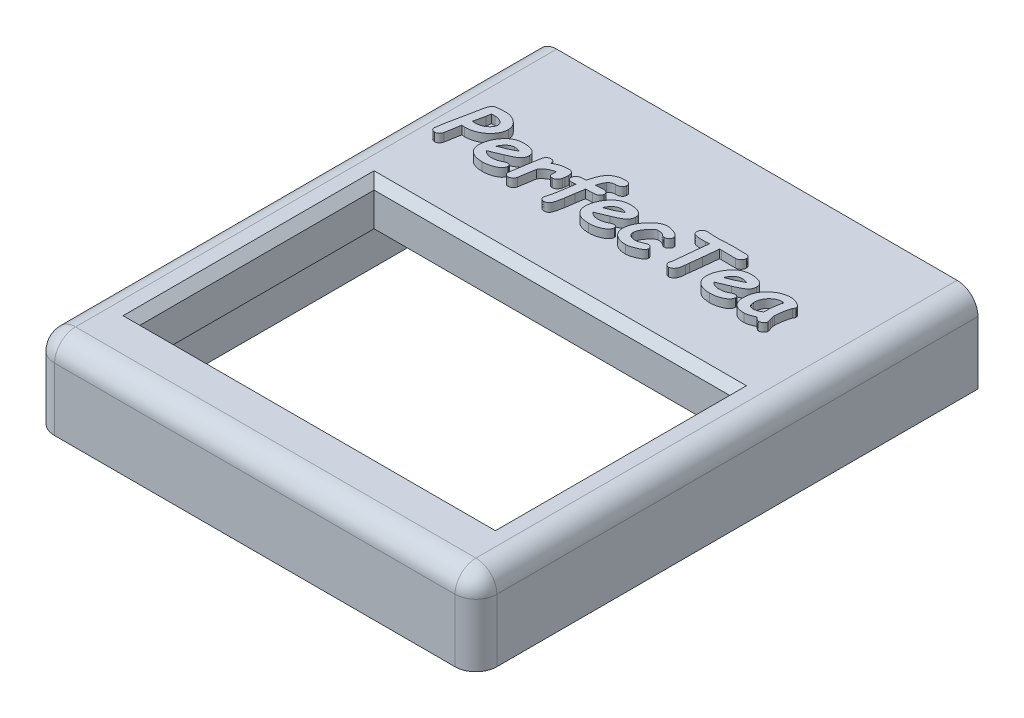
SolidWorks part; units mm, degrees
ref_plane "Front Plane" through (0, 0, 0) normal (0, 0, 1) x (1, 0, 0)
ref_plane "Top Plane" through (0, 0, 0) normal (0, 1, 0) x (1, 0, 0)
ref_plane "Right Plane" through (0, 0, 0) normal (1, 0, 0) x (0, 0, -1)
sketch "Sketch1" plane through (0, 0, 0) normal (0, 1, 0) x (1, 0, 0)
  line L0 (0, 60) -> (0, -60) construction
  line L1 (-52.85, 60) -> (52.85, 60)
  line L2 (-52.85, 60) -> (-52.85, -60)
  line L3 (-52.85, -60) -> (52.85, -60)
  line L4 (52.85, 60) -> (52.85, -60)
  line L5 (-52.85, 0) -> (52.85, 0) construction
  point P8 (0, 0)
  dimension "D1" = 120
  dimension "D2" = 105.7
extrude "Boss-Extrude1" add sketch "Sketch1" against normal blind 25
sketch "Sketch2" plane through (0, 0, 0) normal (0, 1, 0) x (1, 0, 0)
  line L0 (-52.85, -45) -> (52.85, -45) construction
  line L1 (-52.85, 60) -> (-52.85, -60) construction
  line L2 (52.85, -60) -> (52.85, 60) construction
  line L3 (-52.85, -60) -> (52.85, -60) construction
  line L4 (-52.85, 11) -> (52.85, 11) construction
  line L5 (-42.4862, 11) -> (-42.4862, -45) construction
  line L6 (42.5138, -45) -> (42.5138, 11) construction
  line L7 (-47.85, 60) -> (-47.85, -60) construction
  line L8 (52.85, 60) -> (-52.85, 60) construction
  line L9 (47.85, 60) -> (47.85, -60) construction
  line L10 (-45.85, 60) -> (-45.85, -60) construction
  line L11 (45.85, 60) -> (45.85, -60) construction
  line L13 (-42.4862, 11) -> (42.5138, 11)
  line L14 (-42.4862, 11) -> (-42.4862, -45)
  line L15 (-42.4862, -45) -> (42.5138, -45)
  line L16 (42.5138, 11) -> (42.5138, -45)
  point P23 (42.5138, -45)
  dimension "D1" = 15
  dimension "D2" = 56
  dimension "D4" = 10.3638
  dimension "D5" = 5
  dimension "D6" = 5
  dimension "D7" = 2
  dimension "D8" = 2
  dimension "D9" = 85
extrude "Cut-Extrude1" cut sketch "Sketch2" against normal blind 25
sketch "Sketch3" plane through (0, -25, 0) normal (0, -1, 0) x (1, 0, 0)
  line L0 (-42.4862, -11) -> (-42.4862, -60) construction
  line L1 (52.85, -60) -> (-52.85, -60) construction
  line L2 (42.5138, -11) -> (42.5138, -60) construction
  line L3 (-42.4862, -13) -> (42.5138, -13) construction
  line L4 (42.5138, -11) -> (-42.4862, -11) construction
  line L5 (-47.55, -60) -> (-47.55, 60) construction
  line L6 (-52.85, 60) -> (52.85, 60) construction
  line L7 (47.55, 60) -> (47.55, -60) construction
  line L8 (52.85, 60) -> (52.85, -60) construction
  line L9 (-52.85, -60) -> (-52.85, 60) construction
  line L10 (-52.85, -54.7) -> (52.85, -54.7) construction
  line L11 (-52.85, 54.7) -> (52.85, 54.7) construction
  line L13 (-52.85, 60) -> (-47.55, 60)
  line L14 (-52.85, 60) -> (-52.85, -60)
  line L15 (-52.85, -60) -> (-47.55, -60)
  line L16 (-47.55, 60) -> (-47.55, -60)
  line L17 (47.55, 60) -> (52.85, 60)
  line L18 (47.55, 60) -> (47.55, -60)
  line L19 (47.55, -60) -> (52.85, -60)
  line L20 (52.85, 60) -> (52.85, -60)
  line L21 (-47.55, 60) -> (47.55, 60)
  line L22 (-47.55, 60) -> (-47.55, 54.7)
  line L23 (-47.55, 54.7) -> (47.55, 54.7)
  line L24 (47.55, 60) -> (47.55, 54.7)
  line L25 (-47.55, -54.7) -> (47.55, -54.7)
  line L26 (-47.55, -54.7) -> (-47.55, -60)
  line L27 (-47.55, -60) -> (47.55, -60)
  line L28 (47.55, -54.7) -> (47.55, -60)
  point P26 (47.55, 54.7)
  point P28 (47.55, -54.7)
  point P29 (-47.55, -54.7)
  point P30 (-47.55, 54.7)
  line M9 (-52.85, 60) -> (-52.85, -60)
  line M10 (-52.85, -60) -> (52.85, -60)
  line M11 (52.85, -60) -> (52.85, 60)
  line M12 (52.85, 60) -> (-52.85, 60)
  dimension "D1" = 2
  dimension "D2" = 5.3
  dimension "D3" = 5.3
  dimension "D4" = 5.3
  dimension "D5" = 5.3
extrude "Cut-Extrude3" cut sketch "Sketch3" against normal blind 5 contours L16 M12 M9 M10 | L16 L23 L18 M12 | L18 M12 M10 M11 | L25 L16 L18 M10 region at (-50.2, -25, 0) region at (0, -25, 57.35) region at (50.2, -25, 0) region at (0, -25, -57.35)
sketch "Sketch5" plane through (0, -25, 0) normal (0, -1, 0) x (1, 0, 0)
  line L0 (-42.4862, -11) -> (-42.4862, -54.7) construction
  line L1 (-47.55, -54.7) -> (47.55, -54.7) construction
  line L2 (42.5138, -11) -> (42.5138, -54.7) construction
  line L3 (-42.4862, -13) -> (42.5138, -13) construction
  line L4 (42.5138, -11) -> (-42.4862, -11) construction
  line L5 (42.5138, -49.7) -> (-42.4862, -49.7) construction
  line L6 (-47.55, -54.7) -> (47.55, -54.7) construction
  line L8 (42.5138, -49.7) -> (-42.4862, -49.7)
  line L9 (42.5138, -49.7) -> (42.5138, -13)
  line L10 (42.5138, -13) -> (-42.4862, -13)
  line L11 (-42.4862, -49.7) -> (-42.4862, -13)
  dimension "D1" = 2
  dimension "D2" = 5
extrude "Cut-Extrude4" cut sketch "Sketch5" against normal blind 23 contours L10 L11 L8 L9
fillet "Fillet2" radius 5 1 edges at (-52.85, 0, 0)
fillet "Fillet3" radius 5 4 edges at (2.5, 0, 60) (-51.3855, -1.4645, 60) (-52.85, -12.5, 60) (52.85, -10, 60)
fillet "Fillet4" radius 5 2 edges at (51.3855, -1.4645, 58.5355) (52.85, 0, -2.5)
sketch "Sketch7" plane through (0, 0, 0) normal (0, 1, 0) x (1, 0, 0)
  line L0 (0.0138, 11) -> (0, 60) construction
  line L1 (42.5138, 11) -> (-42.4862, 11) construction
  line L2 (47.85, 60) -> (-47.85, 60) construction
  text T0 "PerfecTea" font "Comic Sans MS" height in points 48
extrude "Boss-Extrude2" add sketch "Sketch7" along normal blind 2
sketch "Sketch9" plane through (0, -25, 0) normal (0, -1, 0) x (1, 0, 0)
  line L0 (-47.55, -54.7) -> (47.55, -54.7) construction
  line L1 (-47.55, 54.7) -> (47.55, 54.7) construction
  line L2 (-47.55, 54.7) -> (-47.55, -54.7) construction
  line L3 (-42.4862, -11) -> (-42.4862, -13) construction
  line L4 (42.5138, -13) -> (-42.4862, -13) construction
  line L6 (47.55, 54.7) -> (47.55, -54.7) construction
  line L7 (-45.55, -54.7) -> (-42.4862, -54.7)
  line L8 (-45.55, -54.7) -> (-45.55, 54.7)
  line L9 (-45.55, 54.7) -> (-42.4862, 54.7)
  line L10 (-42.4862, -54.7) -> (-42.4862, 54.7)
  line L11 (47.55, 54.7) -> (47.55, -54.7) construction
  line L12 (42.5138, 45) -> (42.5138, -11) construction
  line L13 (46.55, -54.7) -> (42.5138, -54.7)
  line L14 (46.55, -54.7) -> (46.55, 54.7)
  line L15 (46.55, 54.7) -> (42.5138, 54.7)
  line L16 (42.5138, -54.7) -> (42.5138, 54.7)
  line L17 (-42.4862, -11) -> (-42.4862, 45) construction
  point P0 (-45.55, -54.7)
  point P1 (-45.55, 54.7)
  point P12 (46.55, 54.7)
  point P20 (46.55, -54.7)
  dimension "D1" = 2
  dimension "D2" = 2
  dimension "D3" = 1
  dimension "D4" = 1
extrude "Cut-Extrude5" cut sketch "Sketch9" against normal up to vertex (23 mm away) up to point (42.5138, -2, -13)
sketch "Sketch12" plane through (0, -25, 0) normal (0, -1, 0) x (1, 0, 0)
  line L1 (-42.4862, -49.7) -> (42.5138, -49.7)
  line L2 (-42.4862, -49.7) -> (-42.4862, -54.7)
  line L3 (-42.4862, -54.7) -> (42.5138, -54.7)
  line L4 (42.5138, -49.7) -> (42.5138, -54.7)
extrude "Cut-Extrude6" cut sketch "Sketch12" against normal up to vertex (23 mm away) up to point (-42.4862, -2, -49.7)
sketch "Sketch13" plane through (0, -25, 0) normal (0, -1, 0) x (1, 0, 0)
  line L1 (-42.4862, 54.7) -> (42.5138, 54.7)
  line L2 (-42.4862, 54.7) -> (-42.4862, 45)
  line L3 (-42.4862, 45) -> (42.5138, 45)
  line L4 (42.5138, 54.7) -> (42.5138, 45)
extrude "Cut-Extrude7" cut sketch "Sketch13" against normal up to vertex (23 mm away) up to point (42.5138, -2, -11)
sketch "Sketch17" plane through (0, -25, 0) normal (0, -1, 0) x (1, 0, 0)
  line L0 (-42.4862, -13) -> (-42.4862, -11) construction
  line L1 (42.5138, -11) -> (-42.4862, -11) construction
  line L3 (-42.4862, -12) -> (42.5138, -12)
  line L4 (-42.4862, -12) -> (-42.4862, -13)
  line L5 (-42.4862, -13) -> (42.5138, -13)
  line L6 (42.5138, -12) -> (42.5138, -13)
  point P0 (-42.4862, -12)
  dimension "D1" = 1
extrude "Cut-Extrude8" cut sketch "Sketch17" against normal up to vertex (23 mm away) up to point (-42.4862, -2, -13)
sketch "Sketch20" plane through (0, -2, 0) normal (0, -1, 0) x (1, 0, 0)
  line L5 (-43.4862, -12) -> (-42.4862, -12)
  line L6 (43.5138, -12) -> (42.5138, -12)
  line L10 (-43.4862, 46) -> (43.5138, 46)
  line L11 (43.5138, 46) -> (43.5138, -11)
  line L12 (43.5138, -11) -> (43.5138, -12)
  line L13 (-43.4862, -12) -> (-43.4862, -11)
  line L14 (-43.4862, -11) -> (-43.4862, 46)
  line L15 (-43.4862, 46) -> (43.5138, 46)
  line L16 (43.5138, 46) -> (43.5138, -11)
  line L17 (43.5138, -11) -> (43.5138, -12)
  line L18 (-43.4862, -12) -> (-43.4862, -11)
  line L19 (-43.4862, -11) -> (-43.4862, 46)
  line L24 (42.5138, -12) -> (42.5138, -11)
  line L25 (-42.4862, -12) -> (42.5138, -12)
  line L26 (-42.4862, -11) -> (-42.4862, -12)
  line L27 (-42.4862, 45) -> (-42.4862, -11)
  line L28 (42.5138, 45) -> (-42.4862, 45)
  line L29 (42.5138, -11) -> (42.5138, 45)
  line L30 (42.5138, -12) -> (42.5138, -11)
  line L32 (-42.4862, -11) -> (-42.4862, -12)
  line L33 (-42.4862, 45) -> (-42.4862, -11)
  line L34 (42.5138, 45) -> (-42.4862, 45)
  line L35 (42.5138, -11) -> (42.5138, 45)
  point P0 (0, 0)
  dimension "D1" = 1
  dimension "D3" = 0
extrude "Boss-Extrude3" add sketch "Sketch20" along normal up to vertex (23 mm away) up to point (-42.4862, -25, -11)
sketch "Sketch21" plane through (0, 0, 54.7) normal (0, 0, -1) x (-1, 0, 0)
  line L1 (-46.55, -2) -> (45.55, -2)
  line L2 (-46.55, -2) -> (-46.55, -20)
  line L3 (-46.55, -20) -> (45.55, -20)
  line L4 (45.55, -2) -> (45.55, -20)
extrude "Cut-Extrude9" cut sketch "Sketch21" against normal blind 2
sketch "Sketch22" plane through (0, 0, -54.7) normal (0, 0, 1) x (1, 0, 0)
  line L1 (-45.55, -2) -> (46.55, -2)
  line L2 (-45.55, -2) -> (-45.55, -20)
  line L3 (-45.55, -20) -> (46.55, -20)
  line L4 (46.55, -2) -> (46.55, -20)
extrude "Cut-Extrude10" cut sketch "Sketch22" against normal blind 2
sketch "Sketch23" plane through (0, 0, 54.7) normal (0, 0, 1) x (1, 0, 0)
  line L1 (-47.55, -20) -> (-45.55, -20)
  line L2 (-47.55, -20) -> (-47.55, -25)
  line L3 (-47.55, -25) -> (-45.55, -25)
  line L4 (-45.55, -20) -> (-45.55, -25)
  line L5 (46.55, -20) -> (47.55, -20)
  line L6 (46.55, -20) -> (46.55, -25)
  line L7 (46.55, -25) -> (47.55, -25)
  line L8 (47.55, -20) -> (47.55, -25)
extrude "Boss-Extrude4" add sketch "Sketch23" along normal up to vertex (2 mm away) up to point (-45.55, -20, 56.7)
chamfer "Chamfer1" distance 2 angle 45 4 edges at (42.5138, 0, 17) (0.0138, 0, 45) (-42.4862, 0, 17) (0.0138, 0, -11)
sketch "Sketch24" plane through (-47.55, 0, 0) normal (-1, 0, 0) x (0, 0, 1)
  line L0 (-54.7, -20) -> (-54.7, -25) construction
  line L1 (56.7, -20) -> (-54.7, -20) construction
  line L3 (-54.7, -21) -> (56.7, -21)
  line L4 (-54.7, -21) -> (-54.7, -25)
  line L5 (-54.7, -25) -> (56.7, -25)
  line L6 (56.7, -21) -> (56.7, -25)
  point P0 (-54.7, -21)
  dimension "D1" = 1
extrude "Cut-Extrude11" cut sketch "Sketch24" against normal up to vertex (2 mm away) up to point (-45.55, -25, -54.7)
sketch "Sketch25" plane through (47.55, 0, 0) normal (1, 0, 0) x (0, 0, -1)
  line L0 (-56.7, -25) -> (-56.7, -20) construction
  line L1 (-56.7, -20) -> (54.7, -20) construction
  line L3 (-56.7, -21) -> (54.7, -21)
  line L4 (-56.7, -21) -> (-56.7, -25)
  line L5 (-56.7, -25) -> (54.7, -25)
  line L6 (54.7, -21) -> (54.7, -25)
  point P0 (-56.7, -21)
  dimension "D1" = 1
extrude "Cut-Extrude12" cut sketch "Sketch25" against normal blind 2
sketch "Sketch26" plane through (0, 0, -54.7) normal (0, 0, -1) x (-1, 0, 0)
  line L1 (45.55, -20) -> (47.55, -20)
  line L2 (45.55, -20) -> (45.55, -21)
  line L3 (45.55, -21) -> (47.55, -21)
  line L4 (47.55, -20) -> (47.55, -21)
  line L5 (-47.55, -20) -> (-46.55, -20)
  line L6 (-47.55, -20) -> (-47.55, -21)
  line L7 (-47.55, -21) -> (-46.55, -21)
  line L8 (-46.55, -20) -> (-46.55, -21)
extrude "Boss-Extrude5" add sketch "Sketch26" along normal up to vertex (2 mm away) up to point (-45.55, -20, -56.7)
sketch "Sketch27" plane through (0, -25, 0) normal (0, -1, 0) x (1, 0, 0)
  line L0 (43.5138, -12) -> (-43.4862, -12) construction
  line L1 (-43.4862, 46) -> (-42.4862, 46)
  line L2 (-43.4862, 46) -> (-43.4862, -12)
  line L3 (-43.4862, -12) -> (-42.4862, -12)
  line L4 (-42.4862, 46) -> (-42.4862, -12)
  line L5 (43.5138, 46) -> (-43.4862, 46) construction
  line L6 (42.5138, 46) -> (43.5138, 46)
  line L7 (42.5138, 46) -> (42.5138, -12)
  line L8 (42.5138, -12) -> (43.5138, -12)
  line L9 (43.5138, 46) -> (43.5138, -12)
  line L10 (43.5138, -12) -> (43.5138, 46) construction
  line L11 (-42.4862, -11) -> (-42.4862, 45) construction
  line L12 (42.5138, 45) -> (42.5138, -11) construction
  line L14 (42.5138, 46) -> (-42.4862, 46)
  line L15 (42.5138, 46) -> (42.5138, 45)
  line L16 (42.5138, 45) -> (-42.4862, 45)
  line L17 (-42.4862, 46) -> (-42.4862, 45)
  line L18 (-42.4862, -11) -> (42.5138, -11)
  line L19 (-42.4862, -11) -> (-42.4862, -12)
  line L20 (-42.4862, -12) -> (42.5138, -12)
  line L21 (42.5138, -11) -> (42.5138, -12)
  line M9 (-43.4862, -12) -> (43.5138, -12)
  line M10 (43.5138, -12) -> (43.5138, 46)
  line M11 (43.5138, 46) -> (-43.4862, 46)
  line M16 (42.5138, 45) -> (42.5138, -11)
extrude "Cut-Extrude13" cut sketch "Sketch27" against normal blind 15 contours L7 M11 M16 M9 M10 | L2 L3 L4 L1 | L14 L17 L16 L15 | L20 L19 L18 L21 region at (43.0138, -25, 17)
